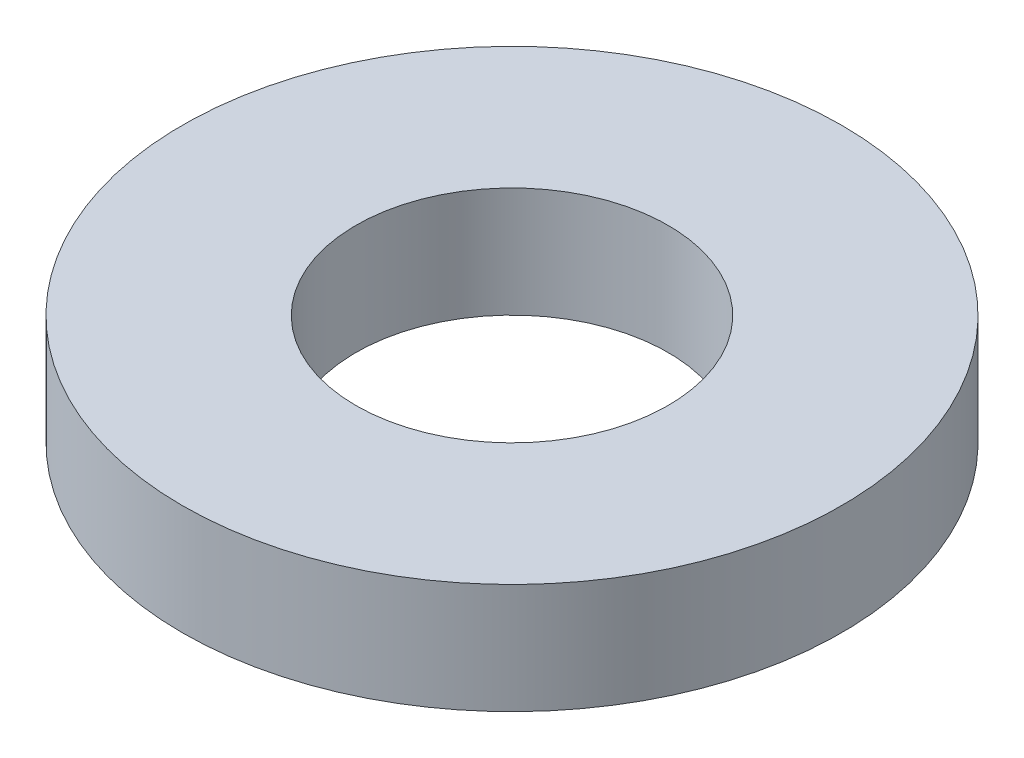
SolidWorks part; units mm, degrees
ref_plane "Front Plane" through (0, 0, 0) normal (0, 0, 1) x (1, 0, 0)
ref_plane "Top Plane" through (0, 0, 0) normal (0, 1, 0) x (1, 0, 0)
ref_plane "Right Plane" through (0, 0, 0) normal (1, 0, 0) x (0, 0, -1)
sketch "Sketch1" plane through (0, 0, 0) normal (0, 1, 0) x (1, 0, 0)
  circle A0 centre (0, 0) radius 2.25
  circle A1 centre (0, 0) radius 4.75
  dimension "D1" = 4.5
  dimension "D2" = 2.5
extrude "Boss-Extrude1" add sketch "Sketch1" along normal blind 1.5875
